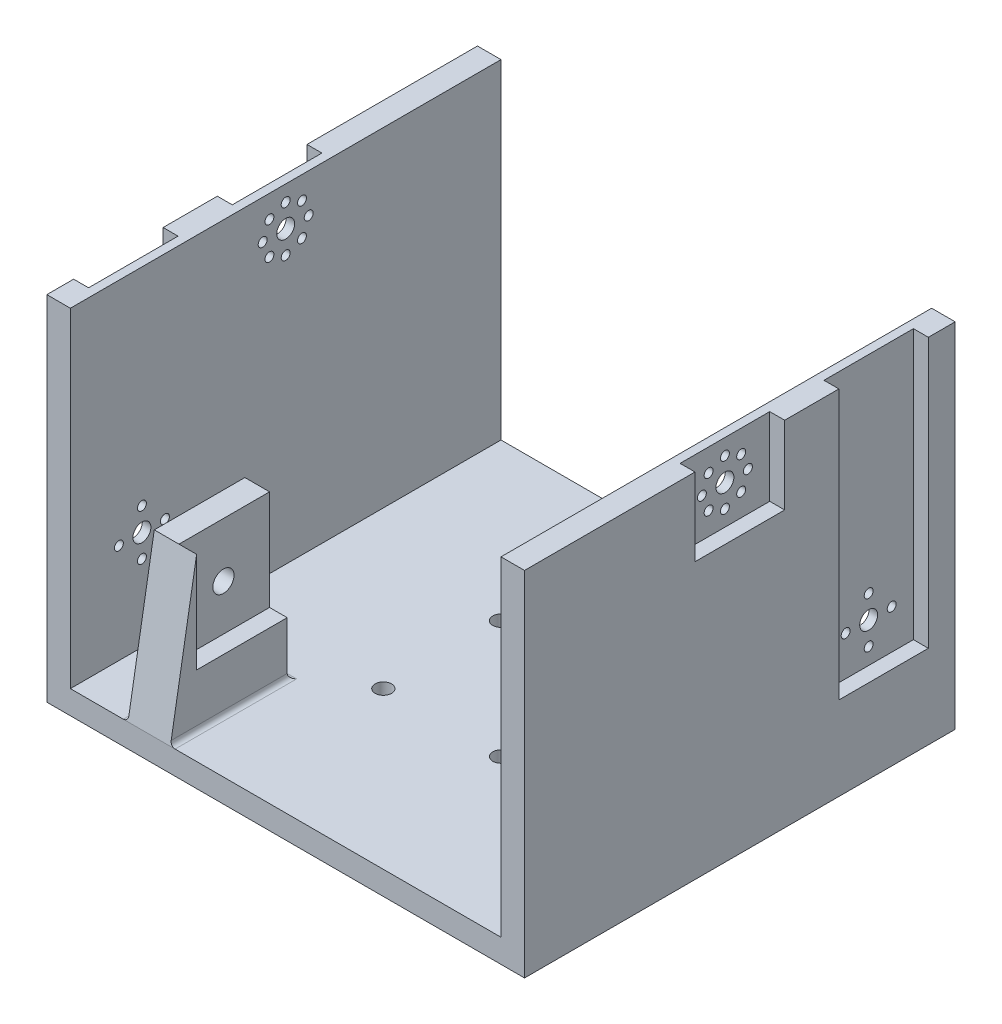
SolidWorks part; units mm, degrees
ref_plane "Front" through (0, 0, 0) normal (0, 0, 1) x (1, 0, 0)
ref_plane "Top" through (0, 0, 0) normal (0, 1, 0) x (1, 0, 0)
ref_plane "Right" through (0, 0, 0) normal (1, 0, 0) x (0, 0, -1)
sketch "Sketch2" plane through (0, 0, 0) normal (0, 1, 0) x (1, 0, 0)
  line L0 (0, 0) -> (0, -91.5) construction
  line L1 (-91.5, -91.5) -> (91.5, -91.5)
  line L2 (-91.5, -91.5) -> (-91.5, 91.5)
  line L3 (-91.5, 91.5) -> (91.5, 91.5)
  line L4 (91.5, -91.5) -> (91.5, 91.5)
  line L5 (0, 0) -> (-91.5, 0) construction
  point P0 (0, 0)
  dimension "D1" = 183
  dimension "D2" = 183
extrude "Boss-Extrude1" add sketch "Sketch2" along normal blind 10
sketch "Sketch3" plane through (0, 0, 0) normal (0, 1, 0) x (1, 0, 0)
  line L0 (-91.5, -91.5) -> (91.5, -91.5) construction
  line L1 (-91.5, 91.5) -> (-101.5, 91.5)
  line L2 (-91.5, 91.5) -> (-91.5, -91.5)
  line L3 (-91.5, -91.5) -> (-101.5, -91.5)
  line L4 (-101.5, 91.5) -> (-101.5, -91.5)
  line L5 (0, 0) -> (0, 91.5) construction
  line L6 (91.5, 91.5) -> (-91.5, 91.5) construction
  line L7 (101.5, 91.5) -> (101.5, -91.5)
  line L8 (91.5, -91.5) -> (101.5, -91.5)
  line L9 (91.5, 91.5) -> (91.5, -91.5)
  line L10 (91.5, 91.5) -> (101.5, 91.5)
  dimension "D1" = 10
extrude "Boss-Extrude2" add sketch "Sketch3" along normal blind 150
sketch "Sketch4" plane through (0, 10, 0) normal (0, 1, 0) x (1, 0, 0)
  point P4 (0, 0)
hole_wizard "M6 Clearance Hole1" positions "Sketch5" profile "Sketch6" hole size "M6" standard "ANSI Metric" end condition up to next
sketch "Sketch5" plane through (0, 10, 0) normal (0, 1, 0) x (1, 0, 0)
  line L0 (0, 0) -> (0, 25) construction
  line L1 (0, 25) -> (-25, 25) construction
  line L3 (0, 25) -> (25, 25) construction
  point P0 (-25, 25)
  point P13 (25, 25)
  point P14 (25, -25)
  point P15 (-25, -25)
  dimension "D1" = 25
  dimension "D2" = 4
sketch "Sketch6" plane through (-25, 10, -25) normal (1, 0, 0) x (0, 0, 1)
  line L0 (0, 0) -> (0, 10)
  line L1 (0, 10) -> (3.5, 10)
  line L2 (3.5, 10) -> (3.5, 0)
  line L5 (3.5, 0) -> (0, 0)
  line L11 (0, -6.35) -> (0, 107.95) construction
  dimension "Thru Hole Dia." = 7
  dimension "Thru Hole Depth" = 10
sketch "Sketch7" plane through (91.5, 0, 0) normal (-1, 0, 0) x (0, 0, 1)
  line L0 (-91.5, 150) -> (91.5, 150) construction
  line L1 (0, 133.49) -> (0, 143.269) construction
  line L2 (0, 133.49) -> (0, 143.269) construction
  circle A0 centre (0, 133.49) radius 3.81
  circle A1 centre (0, 143.269) radius 1.8987
  circle A2 centre (6.9148, 140.4048) radius 1.8987
  circle A3 centre (9.779, 133.49) radius 1.8987
  circle A4 centre (6.9148, 126.5752) radius 1.8987
  circle A5 centre (0, 123.711) radius 1.8987
  circle A6 centre (-6.9148, 126.5752) radius 1.8987
  circle A7 centre (-9.779, 133.49) radius 1.8987
  circle A8 centre (-6.9148, 140.4048) radius 1.8987
  point P7 (0, 150)
  dimension "D1" = 7.62
  dimension "D3" = 3.7973
  dimension "D2" = 16.51
  dimension "D6" = 9.779
  dimension "D5" = 8
extrude "Cut-Extrude1" cut sketch "Sketch7" against normal through all both and the other way through all
sketch "Sketch8" plane through (0, 150, 0) normal (0, 1, 0) x (1, 0, 0)
  line L1 (95.15, -19.05) -> (101.5, -19.05)
  line L2 (95.15, -19.05) -> (95.15, 19.05)
  line L3 (95.15, 19.05) -> (101.5, 19.05)
  line L4 (101.5, -19.05) -> (101.5, 19.05)
  line L5 (95.15, -19.05) -> (101.5, 19.05) construction
  line L6 (95.15, 19.05) -> (101.5, -19.05) construction
  line L9 (101.5, -91.5) -> (101.5, 91.5) construction
  line L10 (0, 0) -> (0, 91.5) construction
  line L11 (91.5, 91.5) -> (-91.5, 91.5) construction
  line L13 (-95.15, 19.05) -> (-101.5, -19.05) construction
  line L14 (-95.15, -19.05) -> (-101.5, 19.05) construction
  line L16 (-101.5, -19.05) -> (-101.5, 19.05)
  line L17 (-95.15, 19.05) -> (-101.5, 19.05)
  line L18 (-95.15, -19.05) -> (-95.15, 19.05)
  line L19 (-95.15, -19.05) -> (-101.5, -19.05)
  point P0 (98.325, 0)
  point P12 (101.5, 0)
  point P23 (-98.325, 0)
  dimension "D1" = 38.1
  dimension "D2" = 6.35
extrude "Cut-Extrude2" cut sketch "Sketch8" against normal blind 33.02
sketch "Sketch9" plane through (101.5, 0, 0) normal (1, 0, 0) x (0, 0, -1)
  line L0 (44.5889, 35.5504) -> (50.6849, 35.5504) construction
  line L2 (80.1089, 69.0884) -> (80.1089, 35.5404)
  line L3 (80.1089, 35.5404) -> (42.0889, 35.5404)
  line L4 (42.0889, 69.0884) -> (42.0889, 35.5404)
  line L5 (80.1089, 69.0884) -> (42.0889, 35.5404) construction
  line L6 (80.1089, 35.5404) -> (42.0889, 69.0884) construction
  line L7 (44.5889, 44.6944) -> (44.5889, 35.5504) construction
  line L13 (80.1089, 69.0884) -> (80.1089, 150)
  line L14 (19.05, 150) -> (91.5, 150) construction
  line L15 (80.1089, 150) -> (42.0889, 150)
  line L16 (42.0889, 150) -> (42.0889, 69.0884)
  point P0 (61.0989, 52.3144)
  point P10 (61.0989, 62.0934)
  point P11 (51.3199, 52.3144)
  point P13 (61.0989, 42.5354)
  point P15 (70.8779, 52.3144)
  dimension "D1" = 0.01
  dimension "D2" = 2.5
extrude "Cut-Extrude3" cut sketch "Sketch9" against normal blind 6.35
sketch "Sketch11" plane through (95.15, 0, 0) normal (1, 0, 0) x (0, 0, -1)
  circle A0 centre (61.0989, 52.3144) radius 3.81
  circle A1 centre (0, 133.49) radius 3.81 construction
extrude "Cut-Extrude4" cut sketch "Sketch11" against normal up to next
hole_wizard "#6 Clearance Hole1" positions "Sketch12" profile "Sketch13" hole size "#6" standard "ANSI Inch" end condition up to next
sketch "Sketch12" plane through (95.15, 0, 0) normal (1, 0, 0) x (0, 0, -1)
  point P0 (61.0989, 62.0934)
  point P3 (51.3199, 52.3144)
  point P6 (70.8779, 52.3144)
  point P10 (61.0989, 42.5354)
sketch "Sketch13" plane through (95.15, 62.0934, -61.0989) normal (0, 1, 0) x (0, 0, -1)
  line L0 (0, 0) -> (0, 3.65)
  line L1 (0, 3.65) -> (1.8986, 3.65)
  line L2 (1.8986, 3.65) -> (1.8986, 0)
  line L5 (1.8986, 0) -> (0, 0)
  line L11 (0, -6.35) -> (0, 107.95) construction
  dimension "Thru Hole Dia." = 3.7973
  dimension "Thru Hole Depth" = 3.65
ref_plane "Plane1" through (0, 0, 0) normal (-0.7071, 0, 0.7071) x (0.7071, 0, 0.7071)
ref_axis "Axis1" through (0, 0, 0) along (0, 1, 0)
pattern_circular "CirPattern1" count 2 over 360 about axis through (0, 0, 0) along (0, 1, 0) of "Cut-Extrude3", "Cut-Extrude4", "#6 Clearance Hole1"
sketch "Esquisse1" plane through (0, 10, 0) normal (0, 1, 0) x (1, 0, 0)
  line L1 (45.09, 80.11) -> (68.5, 80.11)
  line L2 (45.09, 80.11) -> (45.09, 42.09)
  line L3 (45.09, 42.09) -> (68.5, 42.09)
  line L4 (68.5, 80.11) -> (68.5, 42.09)
  line L5 (101.5, -91.5) -> (101.5, 91.5) construction
  line L6 (101.5, 91.5) -> (-101.5, 91.5) construction
  point P4 (0, 0)
  point P5 (68.5, 61.1)
  dimension "D1" = 23.41
  dimension "D2" = 30.4
  dimension "D3" = 38.02
  dimension "D4" = 33
extrude "Boss.-Extru.1" add sketch "Esquisse1" along normal blind 65.1
sketch "Esquisse3" plane through (0, 75.1, 0) normal (0, 1, 0) x (1, 0, 0)
  line L0 (45.09, 42.09) -> (56.09, 42.09)
  line L1 (45.09, 42.09) -> (68.5, 42.09) construction
  line L2 (56.09, 42.09) -> (56.09, 80.11)
  line L3 (68.5, 80.11) -> (45.09, 80.11) construction
  line L4 (56.09, 80.11) -> (45.09, 80.11)
  line L5 (45.09, 80.11) -> (45.09, 42.09)
  dimension "D1" = 11
extrude "Enlèv. mat.-Extru.1" cut sketch "Esquisse3" against normal blind 39.56
sketch "Esquisse4" plane through (56.09, 0, 0) normal (-1, 0, 0) x (0, 0, 1)
  circle A0 centre (-61.281, 51.9838) radius 4.5
  dimension "D1" = 9
extrude "Enlèv. mat.-Extru.2" cut sketch "Esquisse4" against normal up to next
sketch "Esquisse5" plane through (0, 10, 0) normal (0, 1, 0) x (1, 0, 0)
  line L1 (68.5, 42.09) -> (45.0859, 42.09)
  line L2 (68.5, 42.09) -> (68.5, 35.7298)
  line L3 (68.5, 35.7298) -> (45.0859, 35.7298)
  line L4 (45.0859, 42.09) -> (45.0859, 35.7298)
extrude "Boss.-Extru.2" add sketch "Esquisse5" along normal blind 65.26
sketch "Esquisse6" plane through (45.0859, 0, 0) normal (-1, 0, 0) x (0, 0, 1)
  line L0 (-35.7298, 10) -> (-35.7298, 75.26)
  line L1 (-35.7298, 75.26) -> (4.2702, 10)
  line L2 (4.2702, 10) -> (-35.7298, 10)
  dimension "D1" = 40
extrude "Boss.-Extru.3" add sketch "Esquisse6" against normal up to vertex (23.4141 mm away) up to point (68.5, 75.26, -35.7298)
fillet "Congé4" radius 2 3 edges at (68.5, 10, -37.9199) (45.0859, 10, -18.9099) (56.7929, 10, 4.2702)
fillet "Congé5" radius 2 1 edges at (45.09, 10, -61.1)
sketch "Esquisse8" plane through (0, 10, 0) normal (0, 1, 0) x (1, 0, 0)
  line L0 (-91.5, -91.5) -> (91.5, -91.5) construction
  line L1 (-67, -41.85) -> (-49, -41.85)
  line L2 (-67, -41.85) -> (-67, -80.35)
  line L3 (-67, -80.35) -> (-49, -80.35)
  line L4 (-49, -41.85) -> (-49, -80.35)
  line L5 (-101.5, -80.1089) -> (-101.5, -91.5) construction
  point P4 (-67, -61.1)
  dimension "D1" = 30.4
  dimension "D2" = 34.5
  dimension "D3" = 18
  dimension "D4" = 38.5
extrude "Boss.-Extru.4" add sketch "Esquisse8" along normal blind 65.1
sketch "Esquisse9" plane through (0, 75.1, 0) normal (0, 1, 0) x (1, 0, 0)
  line L0 (-49, -41.85) -> (-56.5, -41.85)
  line L1 (-49, -41.85) -> (-67, -41.85) construction
  line L2 (-56.5, -41.85) -> (-56.5, -80.35)
  line L3 (-67, -80.35) -> (-49, -80.35) construction
  line L4 (-56.5, -80.35) -> (-49, -80.35)
  line L5 (-49, -80.35) -> (-49, -41.85)
  dimension "D1" = 7.5
extrude "Enlèv. mat.-Extru.4" cut sketch "Esquisse9" against normal blind 42.56
sketch "Esquisse10" plane through (-56.5, 0, 0) normal (1, 0, 0) x (0, 0, -1)
  circle A0 centre (-61.4583, 52.0176) radius 4.5
  point P2 (-62.1699, 52.4057)
  point P3 (0, 0)
  point P4 (-61.4583, 52.0176)
  dimension "D1" = 9
extrude "Enlèv. mat.-Extru.5" cut sketch "Esquisse10" against normal up to next
sketch "Esquisse12" plane through (-67, 0, 0) normal (-1, 0, 0) x (0, 0, 1)
  line L0 (80.35, 10) -> (80.35, 75.1)
  line L1 (80.35, 75.1) -> (91.5, 10)
  arc A0 (91.5, 10) -> (80.35, 10) centre (85.925, 42.55) cw
  point P6 (0, 0)
  dimension "D1" = 65.1
extrude "Boss.-Extru.5" add sketch "Esquisse12" against normal up to vertex (18 mm away) up to point (-49, 10, 80.35)
fillet "Congé6" radius 2 3 edges at (-67, 10, 66.675) (-49, 10, 66.675) (-58, 10, 41.85)
equation "\"Longueur\"= 183"
equation "\"D2@Sketch2\"=\"Longueur\""
equation "\"Largeur\"= 183"
equation "\"D1@Sketch2\"=\"Largeur\""
